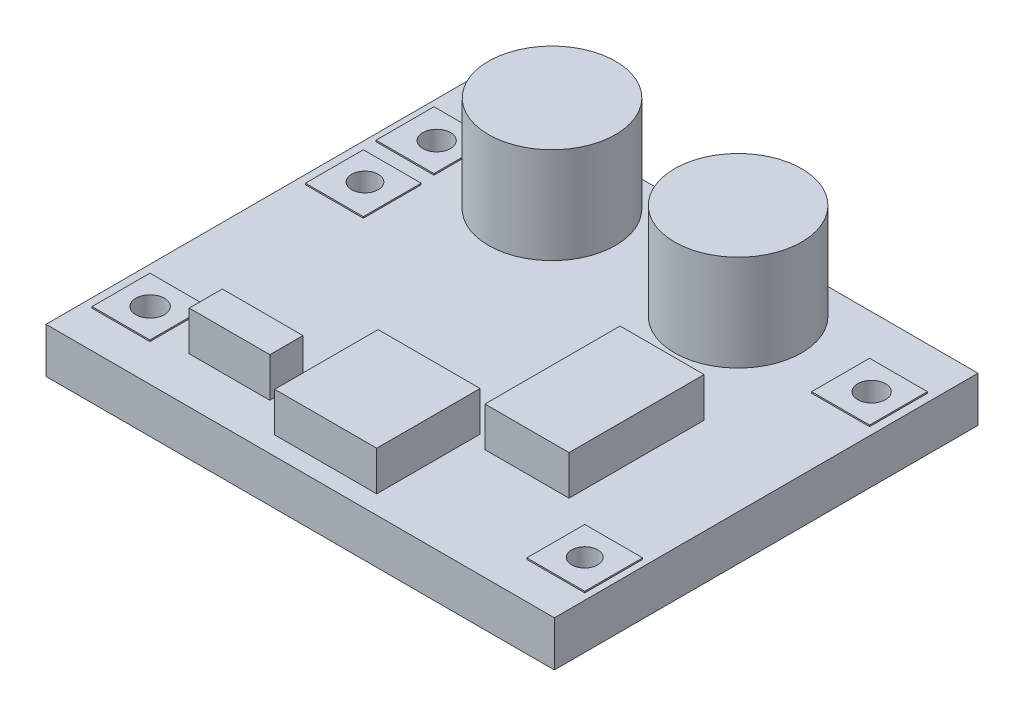
SolidWorks part; units mm, degrees
ref_plane "Front Plane" through (0, 0, 0) normal (0, 0, 1) x (1, 0, 0)
ref_plane "Top Plane" through (0, 0, 0) normal (0, 1, 0) x (1, 0, 0)
ref_plane "Right Plane" through (0, 0, 0) normal (1, 0, 0) x (0, 0, -1)
sketch "Sketch1" plane through (0, 0, 0) normal (0, 1, 0) x (1, 0, 0)
  line L0 (35.5941, 70.9299) -> (177.9707, 70.9299) construction
  line L1 (447.5882, 85.7435) -> (447.5882, 70.7435) construction
  line L7 (429.5099, 85.7432) -> (447.5099, 85.7432)
  line L8 (429.5099, 85.7432) -> (429.5099, 70.7432)
  line L9 (429.5099, 70.7432) -> (447.5099, 70.7432)
  line L10 (447.5099, 85.7432) -> (447.5099, 70.7432)
  line L11 (429.7574, 82.1828) -> (431.8068, 82.1828)
  line L12 (429.7574, 82.1828) -> (429.7574, 84.2323)
  line L13 (429.7574, 84.2323) -> (431.8068, 84.2323)
  line L14 (431.8068, 82.1828) -> (431.8068, 84.2323)
  line L15 (429.8262, 81.6628) -> (431.8757, 81.6628)
  line L16 (429.8262, 81.6628) -> (429.8262, 79.6134)
  line L17 (429.8262, 79.6134) -> (431.8757, 79.6134)
  line L18 (431.8757, 81.6628) -> (431.8757, 79.6134)
  line L19 (429.8312, 74.102) -> (431.8807, 74.102)
  line L20 (429.8312, 74.102) -> (429.8312, 72.0525)
  line L21 (429.8312, 72.0525) -> (431.8807, 72.0525)
  line L22 (431.8807, 74.102) -> (431.8807, 72.0525)
  line L23 (445.1809, 84.2323) -> (447.2304, 84.2323)
  line L24 (445.1809, 84.2323) -> (445.1809, 82.1828)
  line L25 (445.1809, 82.1828) -> (447.2304, 82.1828)
  line L26 (447.2304, 84.2323) -> (447.2304, 82.1828)
  line L27 (445.2348, 74.0942) -> (447.2842, 74.0942)
  line L28 (445.2348, 74.0942) -> (445.2348, 72.0448)
  line L29 (445.2348, 72.0448) -> (447.2842, 72.0448)
  line L30 (447.2842, 74.0942) -> (447.2842, 72.0448)
  line L31 (441.1256, 79.4533) -> (444.1032, 79.4533)
  line L32 (441.1256, 79.4533) -> (441.1256, 74.6696)
  line L33 (441.1256, 74.6696) -> (444.1032, 74.6696)
  line L34 (444.1032, 79.4533) -> (444.1032, 74.6696)
  line L35 (436.9522, 75.0601) -> (440.5643, 75.0601)
  line L36 (436.9522, 75.0601) -> (436.9522, 71.3992)
  line L37 (436.9522, 71.3992) -> (440.5643, 71.3992)
  line L38 (440.5643, 75.0601) -> (440.5643, 71.3992)
  line L39 (432.9495, 73.5469) -> (435.8051, 73.5469)
  line L40 (432.9495, 73.5469) -> (432.9495, 72.3754)
  line L41 (432.9495, 72.3754) -> (435.8051, 72.3754)
  line L42 (435.8051, 73.5469) -> (435.8051, 72.3754)
  circle A0 centre (430.843, 83.2432) radius 0.4913
  circle A1 centre (430.843, 80.7032) radius 0.4729
  circle A2 centre (430.856, 73.0832) radius 0.5063
  circle A3 centre (446.2439, 83.2432) radius 0.4918
  circle A4 centre (446.2439, 73.0832) radius 0.4622
  circle A5 centre (434.9264, 83.2432) radius 2.25
  circle A6 centre (441.5161, 83.2432) radius 2.25
  dimension "D4" = 4.5
  dimension "D1" = 15
  dimension "D2" = 15
  dimension "D3" = 18
  dimension "D5" = 2.5
  dimension "D6" = 2.54
  dimension "D7" = 10.16
  dimension "D8" = 2.5
  dimension "D9" = 10.16
extrude "Boss-Extrude1" add sketch "Sketch1" along normal blind 1.6 contours L10 L7 L8 L9 A6 A5 L14 L11 L12 L13 L15 L18 L17 L16 L19 L22 L21 L20 L23 L26 L25 L24 L27 L30 L29 L28 L31 L34 L33 L32 L35 L38 L37 L36 L39 L42 L41 L40 region at (438.4733, 0, -77.886)
extrude "Boss-Extrude2" add sketch "Sketch1<3>" along normal blind 1.65 and the other way blind 0.05 contours L11 L14 L13 L12 A0 | L18 L15 L16 L17 A1 | L26 L23 L24 L25 A3 | L30 L27 L28 L29 A4 | L22 L19 L20 L21 A2 region at (429.7864, 0, -83.2076) region at (430.851, 0, -81.6338) region at (430.856, 0, -74.073) region at (446.2056, 0, -84.2033) region at (446.2595, 0, -74.0652)
sketch "Sketch1<3>" plane through (0, 0, 0) normal (0, 1, 0) x (1, 0, 0) same geometry as "Sketch1"
extrude "Boss-Extrude3" add sketch "Sketch1<4>" along normal blind 5 contours A5 | A6 region at (434.9264, 0, -83.2432) region at (441.5161, 0, -83.2432)
sketch "Sketch1<4>" plane through (0, 0, 0) normal (0, 1, 0) x (1, 0, 0) same geometry as "Sketch1"
extrude "Boss-Extrude4" add sketch "Sketch1<5>" along normal blind 3 contours L34 L31 L32 L33 | L42 L39 L40 L41 | L35 L38 L37 L36 region at (442.6144, 0, -77.0614) region at (434.3773, 0, -72.9612)
sketch "Sketch1<5>" plane through (0, 0, 0) normal (0, 1, 0) x (1, 0, 0) same geometry as "Sketch1"
